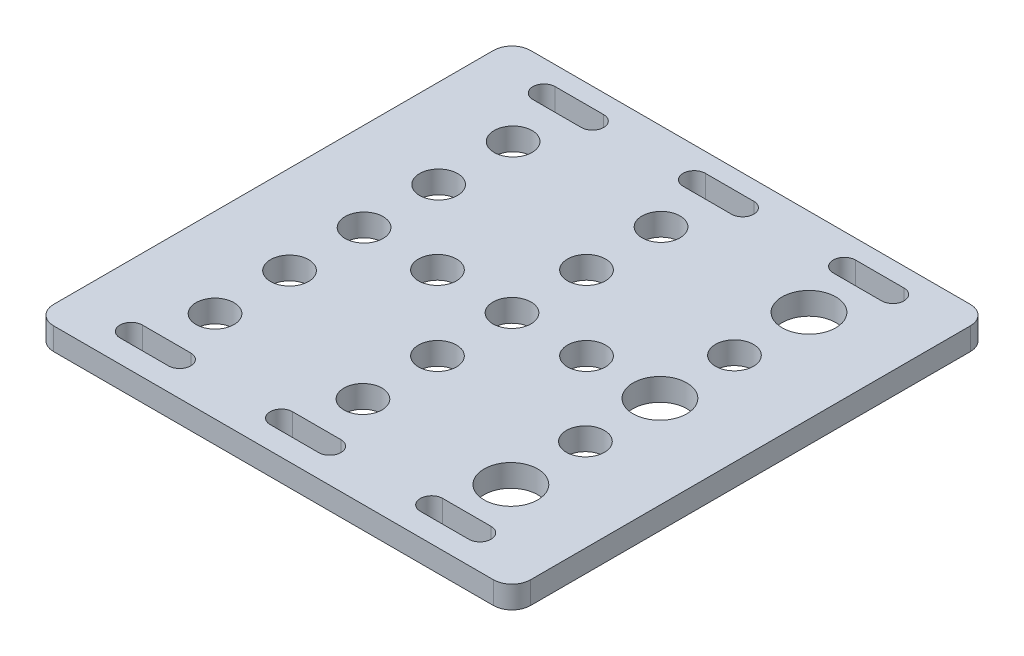
SolidWorks part; units mm, degrees
material "ABS"
ref_plane "Front Plane" through (0, 0, 0) normal (0, 0, 1) x (1, 0, 0)
ref_plane "Top Plane" through (0, 0, 0) normal (0, 1, 0) x (1, 0, 0)
ref_plane "Right Plane" through (0, 0, 0) normal (1, 0, 0) x (0, 0, -1)
sketch "Sketch1" plane through (0, 0, 0) normal (0, 1, 0) x (1, 0, 0)
  line L0 (-20.1, 20.25) -> (23.2, 20.25) construction
  line L1 (-20.1, -19.75) -> (19.6, -19.75) construction
  line L2 (29.5, 32) -> (-29.5, 32)
  line L3 (-32, 29.5) -> (-32, -29.5)
  line L4 (-29.5, -32) -> (29.5, -32)
  line L5 (32, -29.5) -> (32, 29.5)
  line L6 (3, 26.45) -> (-3.5, 26.45)
  line L7 (-23.65, 29.45) -> (-17.15, 29.45)
  line L8 (-17.15, 26.45) -> (-23.65, 26.45)
  line L9 (-3.5, 29.45) -> (3, 29.45)
  line L10 (16.65, 29.45) -> (23.15, 29.45)
  line L11 (23.15, 26.45) -> (16.65, 26.45)
  line L12 (-17.15, -28.95) -> (-23.65, -28.95)
  line L13 (-23.65, -25.95) -> (-17.15, -25.95)
  line L14 (-3.5, -25.95) -> (3, -25.95)
  line L15 (3, -28.95) -> (-3.5, -28.95)
  line L16 (23.15, -28.95) -> (16.65, -28.95)
  line L17 (16.65, -25.95) -> (23.15, -25.95)
  line L18 (-0.25, 0.25) -> (-0.25, -9.75) construction
  arc A0 (-29.5, 32) -> (-32, 29.5) centre (-29.5, 29.5) ccw
  arc A1 (-32, -29.5) -> (-29.5, -32) centre (-29.5, -29.5) ccw
  arc A2 (29.5, -32) -> (32, -29.5) centre (29.5, -29.5) ccw
  arc A3 (32, 29.5) -> (29.5, 32) centre (29.5, 29.5) ccw
  circle A4 centre (-10.25, 0.25) radius 2.55
  circle A5 centre (19.6, 0.25) radius 3.6
  arc A6 (-23.65, 29.45) -> (-23.65, 26.45) centre (-23.65, 27.95) ccw
  arc A7 (-17.15, 26.45) -> (-17.15, 29.45) centre (-17.15, 27.95) ccw
  arc A8 (-3.5, 29.45) -> (-3.5, 26.45) centre (-3.5, 27.95) ccw
  arc A9 (3, 26.45) -> (3, 29.45) centre (3, 27.95) ccw
  arc A10 (23.15, 26.45) -> (23.15, 29.45) centre (23.15, 27.95) ccw
  arc A11 (16.65, 29.45) -> (16.65, 26.45) centre (16.65, 27.95) ccw
  circle A12 centre (19.6, 10.25) radius 2.55
  circle A13 centre (-0.25, 10.25) radius 2.55
  arc A14 (-17.15, -28.95) -> (-17.15, -25.95) centre (-17.15, -27.45) ccw
  arc A15 (-23.65, -25.95) -> (-23.65, -28.95) centre (-23.65, -27.45) ccw
  arc A16 (-3.5, -25.95) -> (-3.5, -28.95) centre (-3.5, -27.45) ccw
  arc A17 (3, -28.95) -> (3, -25.95) centre (3, -27.45) ccw
  arc A18 (23.15, -28.95) -> (23.15, -25.95) centre (23.15, -27.45) ccw
  arc A19 (16.65, -25.95) -> (16.65, -28.95) centre (16.65, -27.45) ccw
  circle A20 centre (19.6, -19.75) radius 3.6
  circle A21 centre (-0.25, -9.75) radius 2.55
  circle A22 centre (19.6, -9.75) radius 2.55
  circle A23 centre (9.75, 0.25) radius 2.55
  circle A24 centre (-0.25, 0.25) radius 2.55
  circle A25 centre (-20.1, -19.75) radius 2.55
  circle A26 centre (-20.1, -9.75) radius 2.55
  circle A27 centre (-20.1, 0.25) radius 2.55
  circle A28 centre (-20.1, 10.25) radius 2.55
  circle A29 centre (19.6, 20.25) radius 3.6
  circle A30 centre (-20.1, 20.25) radius 2.55
  circle A31 centre (-0.25, -19.75) radius 2.55
  circle A32 centre (-0.25, 20.25) radius 2.55
  point P83 (0, 0)
extrude "Boss-Extrude1" add sketch "Sketch1" along normal blind 3
